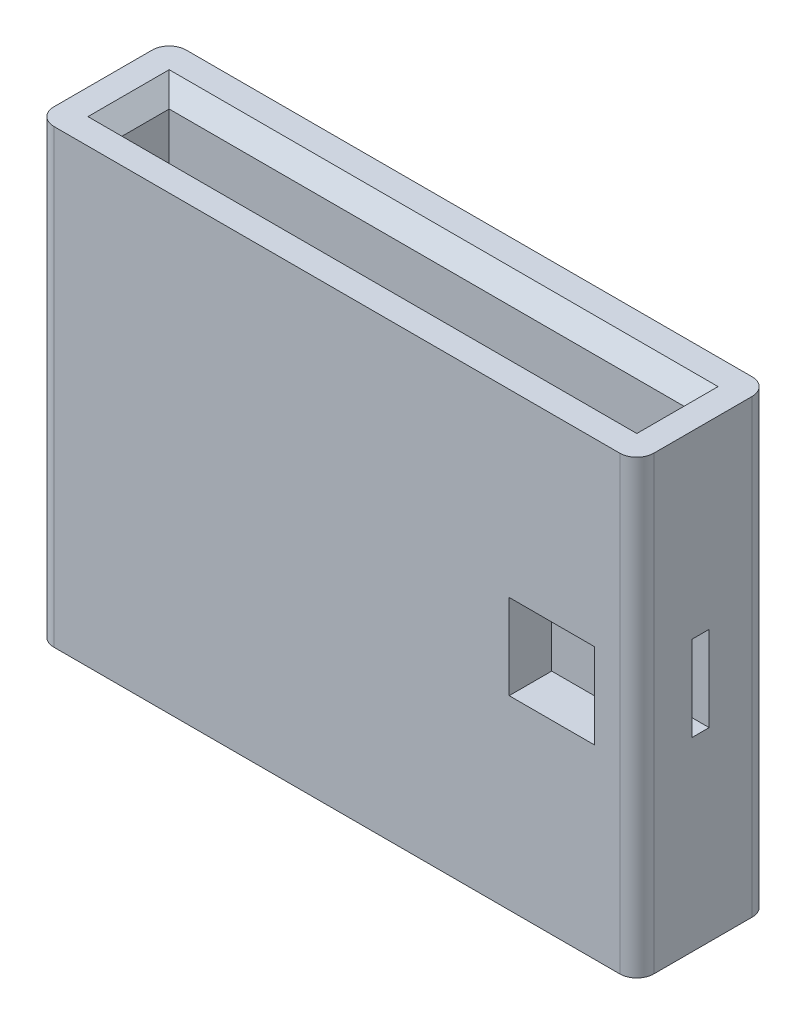
SolidWorks part; units mm, degrees
ref_plane "Front Plane" through (0, 0, 0) normal (0, 0, 1) x (1, 0, 0)
ref_plane "Top Plane" through (0, 0, 0) normal (0, 1, 0) x (1, 0, 0)
ref_plane "Right Plane" through (0, 0, 0) normal (1, 0, 0) x (0, 0, -1)
sketch "Sketch1" plane through (0, 0, 0) normal (0, 1, 0) x (1, 0, 0)
  line L1 (-30.25, -2.775) -> (30.25, -2.775)
  line L2 (-30.25, -2.775) -> (-30.25, 2.775)
  line L3 (-30.25, 2.775) -> (30.25, 2.775)
  line L4 (30.25, -2.775) -> (30.25, 2.775)
  line L5 (-30.25, -2.775) -> (30.25, 2.775) construction
  line L6 (-30.25, 2.775) -> (30.25, -2.775) construction
  point P0 (0, 0)
  dimension "D1" = 60.5
  dimension "D2" = 5.55
extrude "Extrude-Thin1" add sketch "Sketch1" along normal blind 48 thin thin type one direction wall 5
sketch "Sketch2" plane through (0, 0, 0) normal (0, -1, 0) x (1, 0, 0)
  line L1 (-35.25, -7.775) -> (35.25, -7.775)
  line L2 (-35.25, -7.775) -> (-35.25, 7.775)
  line L3 (-35.25, 7.775) -> (35.25, 7.775)
  line L4 (35.25, -7.775) -> (35.25, 7.775)
  line L5 (-35.25, -7.775) -> (35.25, 7.775) construction
  line L6 (-35.25, 7.775) -> (35.25, -7.775) construction
  point P0 (0, 0)
extrude "Boss-Extrude1" add sketch "Sketch2" along normal blind 5
sketch "Sketch4" plane through (0, 0, 7.775) normal (0, 0, 1) x (1, 0, 0)
  line L1 (30.25, 26.82) -> (20.25, 26.82)
  line L2 (30.25, 26.82) -> (30.25, 16.82)
  line L3 (30.25, 16.82) -> (20.25, 16.82)
  line L4 (20.25, 26.82) -> (20.25, 16.82)
  line L5 (35.25, -5) -> (-35.25, -5) construction
  line L6 (35.25, 48) -> (35.25, -5) construction
  point P8 (0, 0)
  dimension "D1" = 10
  dimension "D2" = 10
  dimension "D3" = 21.82
  dimension "D4" = 5
extrude "Excitation Cutout" cut sketch "Sketch4" against normal blind 5
sketch "Sketch6" plane through (35.25, 0, 0) normal (1, 0, 0) x (0, 0, -1)
  line L0 (7.775, -5) -> (-7.775, -5) construction
  line L1 (-1.275, 26.82) -> (0.725, 26.82)
  line L2 (-1.275, 26.82) -> (-1.275, 16.82)
  line L3 (-1.275, 16.82) -> (0.725, 16.82)
  line L4 (0.725, 26.82) -> (0.725, 16.82)
  line L5 (-7.775, 48) -> (-7.775, -5) construction
  dimension "D1" = 21.82
  dimension "D2" = 10
  dimension "D3" = 6.5
  dimension "D4" = 2
extrude "Emission Cutout" cut sketch "Sketch6" against normal up to next
fillet "Fillet1" radius 2 4 edges at (-35.25, 21.5, 7.775) (-35.25, 21.5, -7.775) (35.25, 21.5, -7.775) (35.25, 21.5, 7.775)
chamfer "Chamfer1" distance 2 angle 45 4 edges at (0, 48, -2.775) (30.25, 48, 0) (-30.25, 48, 0) (0, 48, 2.775)
